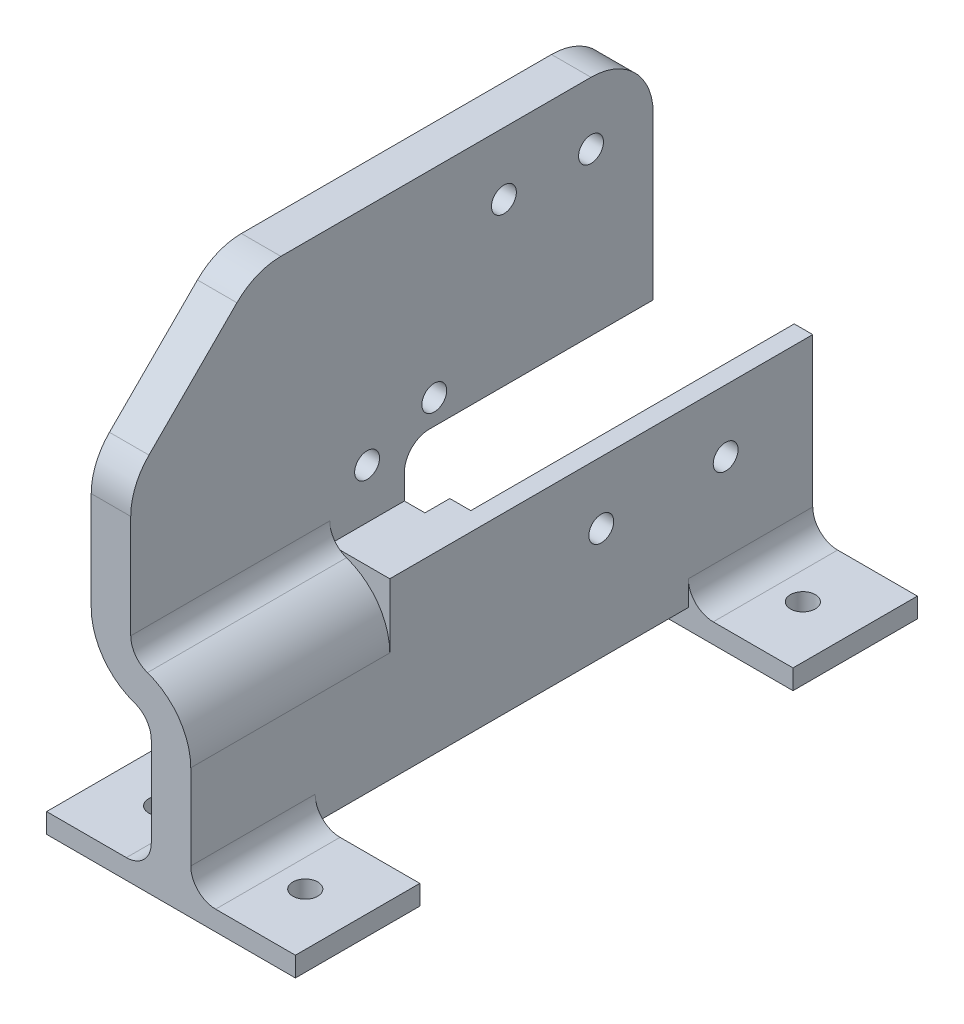
SolidWorks part; units mm, degrees
ref_plane "Front Plane" through (0, 0, 0) normal (0, 0, 1) x (1, 0, 0)
ref_plane "Top Plane" through (0, 0, 0) normal (0, 1, 0) x (1, 0, 0)
ref_plane "Right Plane" through (0, 0, 0) normal (1, 0, 0) x (0, 0, -1)
sketch "Sketch1" plane through (0, 0, 0) normal (0, 0, 1) x (1, 0, 0)
  line L0 (0, 0) -> (0, 110)
  line L1 (0, 110) -> (15.875, 110)
  line L2 (15.875, 110) -> (15.875, 0)
  line L3 (15.875, 0) -> (40, 0)
  line L4 (40, 0) -> (40, -70)
  line L5 (40, -70) -> (24.125, -70)
  line L6 (24.125, -70) -> (24.125, -15.875)
  line L7 (24.125, -15.875) -> (0, -15.875)
  line L8 (0, -15.875) -> (0, 0)
  dimension "D1" = 15.875
  dimension "D2" = 70
  dimension "D3" = 180
  dimension "D4" = 40
extrude "Boss-Extrude1" add sketch "Sketch1" along normal blind 250
sketch "Sketch2" plane through (0, 0, 0) normal (0, 0, -1) x (-1, 0, 0)
  line L1 (-32.0625, -70) -> (-82.0625, -70)
  line L2 (17.9375, -70) -> (17.9375, -77.9375)
  line L3 (17.9375, -77.9375) -> (-82.0625, -77.9375)
  line L4 (-82.0625, -70) -> (-82.0625, -77.9375)
  line L5 (-24.125, -70) -> (-40, -70) construction
  line L6 (-32.0625, -70) -> (17.9375, -70)
  dimension "D1" = 100
  dimension "D2" = 7.9375
extrude "Boss-Extrude2" add sketch "Sketch2" against normal blind 50
sketch "Sketch3" plane through (0, -70, 0) normal (0, 1, 0) x (1, 0, 0)
  line L0 (61.0313, -50) -> (61.0313, 0) construction
  line L1 (40, -50) -> (82.0625, -50) construction
  line L2 (40, 0) -> (82.0625, 0) construction
  circle A0 centre (61.0313, -25) radius 5
extrude "Cut-Extrude1" cut sketch "Sketch3" against normal through all
ref_plane "Plane1" through (32.0625, 0, 0) normal (1, 0, 0) x (0, 0, -1)
mirror "Mirror1" about plane through (32.0625, 0, 0) normal (1, 0, 0) of "Cut-Extrude1"
fillet "Fillet1" radius 10 2 edges at (24.125, -70, 25) (40, -70, 25)
ref_plane "Plane2" through (0, 0, 125) normal (0, 0, -1) x (-1, 0, 0)
mirror "Mirror2" about plane through (0, 0, 125) normal (0, 0, -1) of "Fillet1", "Mirror1", "Boss-Extrude2"
sketch "Sketch4" plane through (15.875, 0, 0) normal (1, 0, 0) x (0, 0, -1)
  line L0 (0, 0) -> (-140, 0)
  line L1 (-250, 0) -> (0, 0) construction
  line L2 (-140, 0) -> (-140, 20)
  line L3 (-140, 20) -> (-40, 20)
  line L4 (-40, 20) -> (-40, 110)
  line L5 (-250, 110) -> (0, 110) construction
  line L6 (-40, 110) -> (0, 110)
  line L7 (0, 110) -> (0, 0)
  dimension "D1" = 40
  dimension "D2" = 140
  dimension "D3" = 20
extrude "Cut-Extrude2" cut sketch "Sketch4" against normal through all
fillet "Fillet2" radius 25 1 edges at (7.9375, 110, 40)
sketch "Sketch5" plane through (15.875, 0, 0) normal (1, 0, 0) x (0, 0, -1)
  line L0 (-250, 60) -> (-250, 110)
  line L1 (-250, 0) -> (-250, 110) construction
  line L2 (-250, 110) -> (-200, 110)
  line L3 (-250, 110) -> (-65, 110) construction
  line L4 (-200, 110) -> (-250, 60)
  dimension "D1" = 50
  dimension "D2" = 45
extrude "Cut-Extrude3" cut sketch "Sketch5" against normal through all
fillet "Fillet3" radius 25 2 edges at (7.9375, 60, 250) (7.9375, 110, 200)
sketch "Sketch6" plane through (40, 0, 0) normal (1, 0, 0) x (0, 0, -1)
  line L0 (-40, 85) -> (-40, 20) construction
  line L1 (-140, 20) -> (-140, 0) construction
  line L2 (-250, 0) -> (0, 0) construction
  line L3 (-40, 20) -> (-140, 20) construction
  line L4 (0, -60) -> (0, 0) construction
  circle A0 centre (-65, 85) radius 5
  circle A1 centre (-100, 85) radius 5
  circle A2 centre (-128, 30) radius 5
  circle A3 centre (-155, 20) radius 5
  circle A4 centre (-35, -25) radius 5
  circle A5 centre (-85, -25) radius 5
  dimension "D5" = 10
  dimension "D8" = 35
  dimension "D1" = 35
  dimension "D2" = 88
  dimension "D3" = 15
  dimension "D4" = 25
  dimension "D6" = 10
  dimension "D7" = 50
extrude "Cut-Extrude4" cut sketch "Sketch6" against normal through all
sketch "Sketch7" plane through (0, 0, 0) normal (0, 0, -1) x (-1, 0, 0)
  line L0 (0, 0) -> (-40, 0)
  line L1 (-40, 0) -> (-40, -40)
  line L2 (-40, -60) -> (-40, 0) construction
  line L3 (-40, -40) -> (-24.125, -40)
  line L4 (-24.125, -15.875) -> (-24.125, -60) construction
  line L5 (-24.125, -40) -> (-24.125, -15.875)
  line L6 (-24.125, -15.875) -> (0, -15.875)
  line L7 (0, -15.875) -> (0, 0)
  dimension "D1" = 40
extrude "Cut-Extrude5" cut sketch "Sketch7" against normal blind 170
fillet "Fillet4" radius 10 1 edges at (7.9375, 20, 140)
fillet "Fillet5" radius 25.875 1 edges at (40, 0, 210)
fillet "Fillet6" radius 10 1 edges at (15.875, 0, 210)
sketch "Sketch8" plane through (0, 0, 170) normal (0, 0, -1) x (-1, 0, 0)
  line L0 (-40, -40) -> (-24.125, -40)
  line L1 (-24.125, -40) -> (-24.125, -15.875)
  line L2 (-24.125, -15.875) -> (0, -15.875)
  line L3 (0, -15.875) -> (0, 0)
  line L4 (0, 0) -> (-40, 0)
  line L5 (-40, 0) -> (-40, -40)
extrude "Boss-Extrude3" add sketch "Sketch8" along normal up to vertex (30 mm away) up to point (0, 0, 140)
sketch "Sketch9" plane through (0, 0, 140) normal (0, 0, -1) x (-1, 0, 0)
  line L1 (-40, 0) -> (-24.125, 0)
  line L2 (-40, 0) -> (-40, -40)
  line L3 (-40, -40) -> (-24.125, -40)
  line L4 (-24.125, 0) -> (-24.125, -40)
extrude "Boss-Extrude4" add sketch "Sketch9" along normal up to vertex (140 mm away) up to point (40, -40, 0)
fillet "Fillet7" radius 25.875 1 edges at (0, -15.875, 195)
fillet "Fillet8" radius 10 1 edges at (24.125, -15.875, 195)
sketch "Sketch10" plane through (0, 0, 0) normal (0, 0, -1) x (-1, 0, 0)
  line L1 (-24.125, 0) -> (-32.561, 0)
  line L2 (-24.125, 0) -> (-24.125, -40)
  line L3 (-24.125, -40) -> (-32.561, -40)
  line L4 (-32.561, 0) -> (-32.561, -40)
  dimension "D1" = 40
extrude "Cut-Extrude6" cut sketch "Sketch10" against normal blind 130
sketch "Sketch11" plane through (40, 0, 0) normal (1, 0, 0) x (0, 0, -1)
  line L1 (0, 0) -> (-170, 0) construction
  line L2 (0, -60) -> (0, 0) construction
  circle A0 centre (-35, -25) radius 5
  circle A1 centre (-85, -25) radius 5
  dimension "D1" = 10
  dimension "D2" = 25
  dimension "D3" = 50
  dimension "D4" = 35
extrude "Cut-Extrude7" cut sketch "Sketch11" against normal through all
